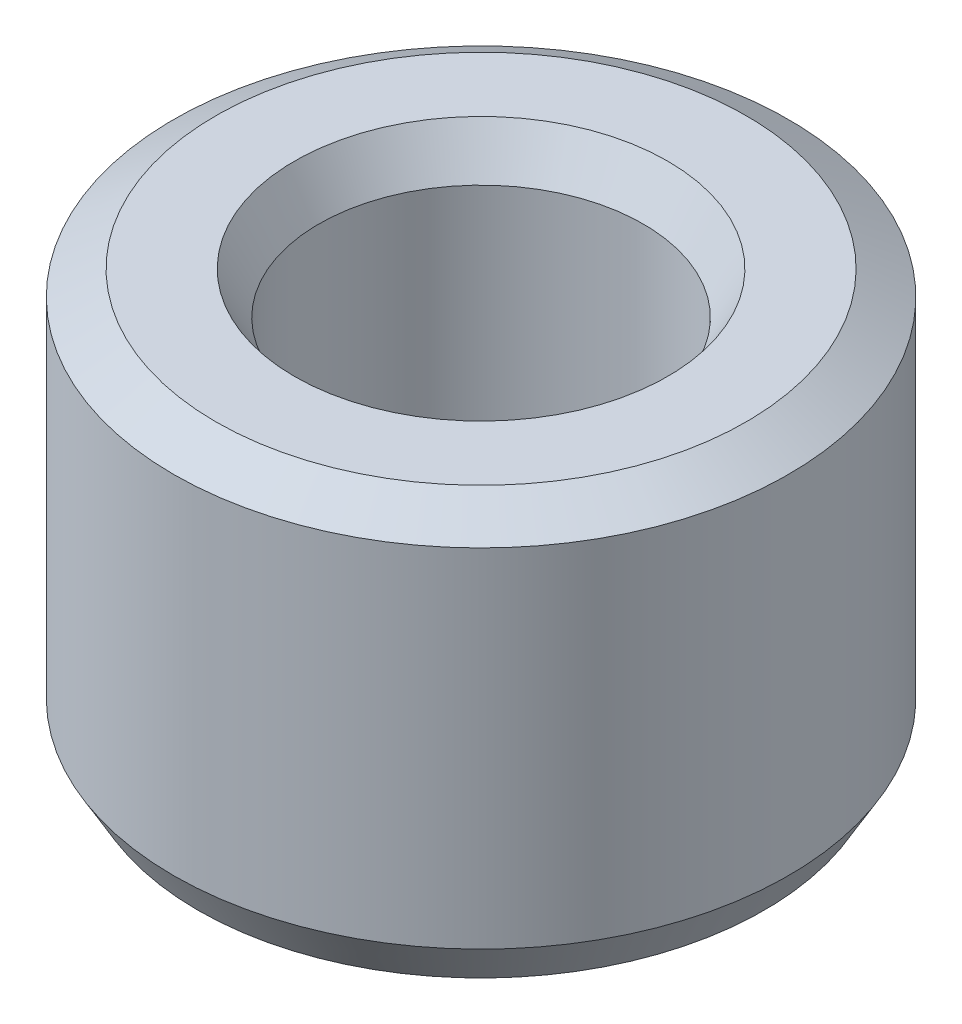
SolidWorks part; units mm, degrees
ref_plane "Front Plane" through (0, 0, 0) normal (0, 0, 1) x (1, 0, 0)
ref_plane "Top Plane" through (0, 0, 0) normal (0, 1, 0) x (1, 0, 0)
ref_plane "Right Plane" through (0, 0, 0) normal (1, 0, 0) x (0, 0, -1)
sketch "Sketch1" plane through (0, 0, 0) normal (0, 1, 0) x (1, 0, 0)
  circle A0 centre (0, 0) radius 5
  dimension "SLEEVE_OD" = 10
extrude "Boss-Extrude1" add sketch "Sketch1" along normal blind 6.7346
sketch "Sketch2" plane through (0, 0, 0) normal (0, 1, 0) x (1, 0, 0)
  circle A0 centre (0, 0) radius 2.6377
  dimension "BORE_D" = 5.2754
extrude "Cut-Extrude1" cut sketch "Sketch2" along normal through all
chamfer "Chamfer1" distance 0.3966 angle 60 4 edges at (0, 6.7346, 2.6377) (0, 0, 2.6377) (0, 0, 5) (0, 6.7346, 5) first distance on face at (0, 6.7346, 2.6377) first distance on face at (0, 0, 2.6377) first distance on face at (0, 6.7346, 5)
